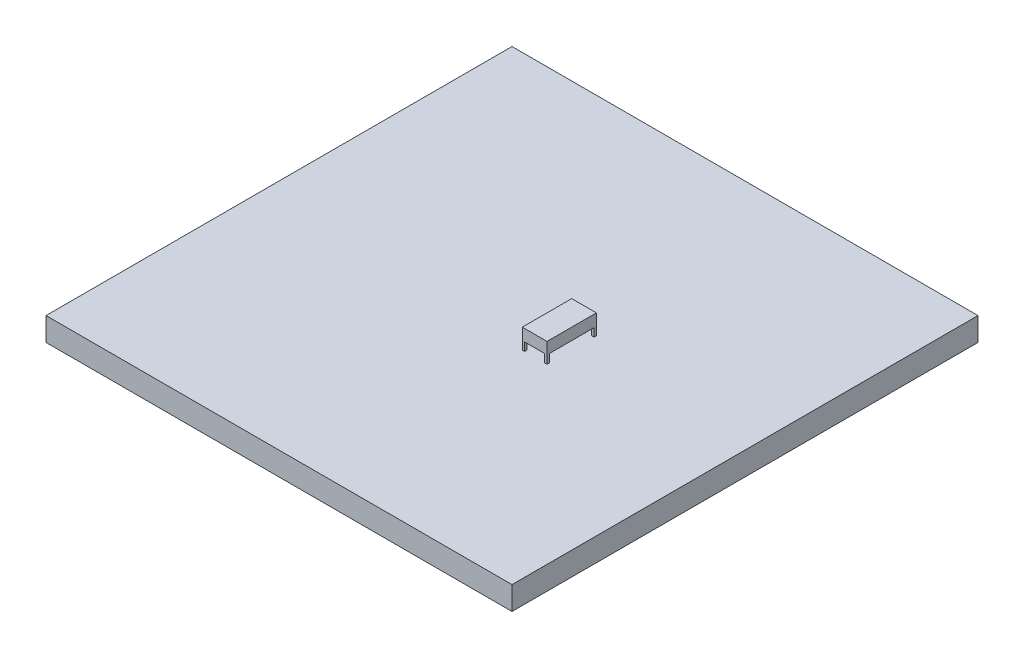
SolidWorks part; units mm, degrees
ref_plane "Front Plane" through (0, 0, 0) normal (0, 0, 1) x (1, 0, 0)
ref_plane "Top Plane" through (0, 0, 0) normal (0, 1, 0) x (1, 0, 0)
ref_plane "Right Plane" through (0, 0, 0) normal (1, 0, 0) x (0, 0, -1)
sketch "Sketch2" plane through (0, 0, 0) normal (0, 1, 0) x (1, 0, 0)
  line L1 (-10000, -10000) -> (10000, -10000)
  line L2 (-10000, -10000) -> (-10000, 10000)
  line L3 (-10000, 10000) -> (10000, 10000)
  line L4 (10000, -10000) -> (10000, 10000)
  line L5 (-10000, -10000) -> (10000, 10000) construction
  line L6 (-10000, 10000) -> (10000, -10000) construction
  point P0 (0, 0)
  dimension "D1" = 20000
  dimension "D2" = 20000
extrude "Boss-Extrude1" add sketch "Sketch2" against normal blind 1000
ref_plane "Plane1" through (0, 350, 0) normal (0, 1, 0) x (1, 0, 0)
sketch "Sketch6" plane through (0, 350, 0) normal (0, 1, 0) x (1, 0, 0)
  line L1 (1501.8441, -1060.1252) -> (2561.9693, -1060.1252)
  line L2 (1501.8441, -1060.1252) -> (1501.8441, 1060.1252)
  line L3 (1501.8441, 1060.1252) -> (2561.9693, 1060.1252)
  line L4 (2561.9693, -1060.1252) -> (2561.9693, 1060.1252)
  line L5 (1501.8441, -1060.1252) -> (2561.9693, 1060.1252) construction
  line L6 (1501.8441, 1060.1252) -> (2561.9693, -1060.1252) construction
  point P0 (2031.9067, 0)
extrude "Boss-Extrude2" add sketch "Sketch6" along normal blind 500 separate body
sketch "Sketch8" plane through (0, 350, 0) normal (0, -1, 0) x (1, 0, 0)
  line L0 (1501.8441, -1060.1252) -> (1501.8441, 1060.1252) construction
  line L1 (1501.8441, 1060.1252) -> (1606.3386, 1060.1252)
  line L2 (1501.8441, 1060.1252) -> (1501.8441, 958.5559)
  line L3 (1501.8441, 958.5559) -> (1606.3386, 958.5559)
  line L4 (1606.3386, 1060.1252) -> (1606.3386, 958.5559)
  line L5 (1501.8441, 1060.1252) -> (2561.9693, 1060.1252) construction
  line L6 (2561.9693, 1060.1252) -> (2561.9693, -1060.1252) construction
  line L7 (2561.9693, 1060.1252) -> (2459.7072, 1060.1252)
  line L8 (2561.9693, 1060.1252) -> (2561.9693, 958.5559)
  line L9 (2561.9693, 958.5559) -> (2459.7072, 958.5559)
  line L10 (2459.7072, 1060.1252) -> (2459.7072, 958.5559)
  line L11 (2561.9693, -1060.1252) -> (1501.8441, -1060.1252) construction
  line L12 (2561.9693, -1060.1252) -> (2459.7072, -1060.1252)
  line L13 (2561.9693, -1060.1252) -> (2561.9693, -962.8058)
  line L14 (2561.9693, -962.8058) -> (2459.7072, -962.8058)
  line L15 (2459.7072, -1060.1252) -> (2459.7072, -962.8058)
  line L17 (1501.8441, -1060.1252) -> (1606.3386, -1060.1252)
  line L18 (1501.8441, -1060.1252) -> (1501.8441, -962.8058)
  line L19 (1501.8441, -962.8058) -> (1606.3386, -962.8058)
  line L20 (1606.3386, -1060.1252) -> (1606.3386, -962.8058)
extrude "Boss-Extrude3" add sketch "Sketch8" along normal up to body
